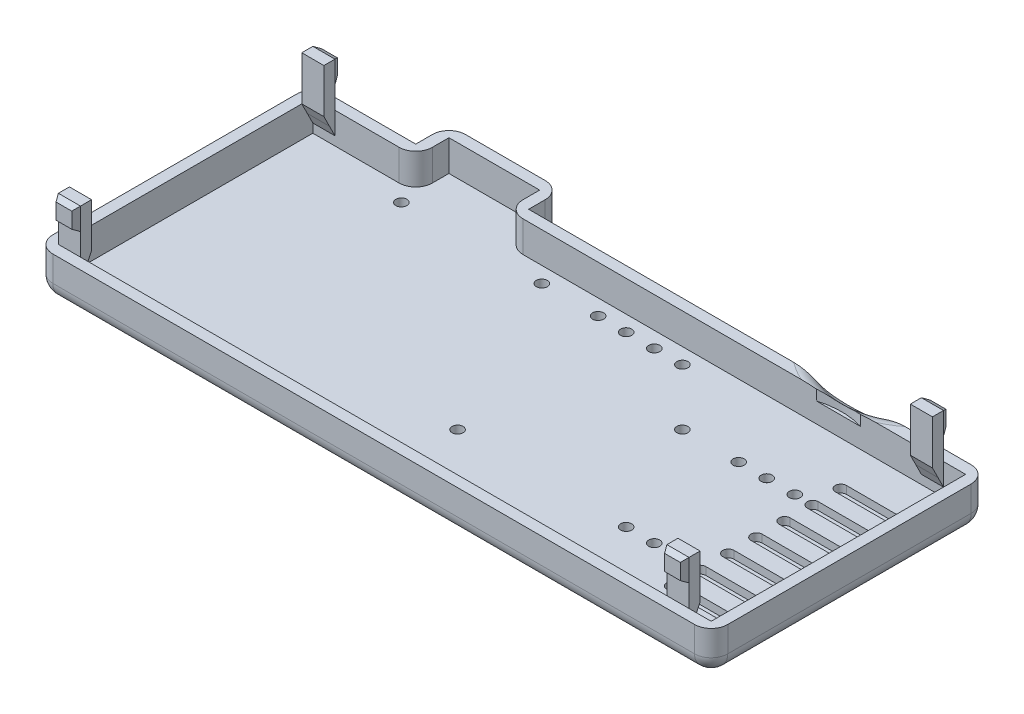
SolidWorks part; units mm, degrees
material "ABS"
ref_plane "Front Plane" through (0, 0, 0) normal (0, 0, 1) x (1, 0, 0)
ref_plane "Top Plane" through (0, 0, 0) normal (0, 1, 0) x (1, 0, 0)
ref_plane "Right Plane" through (0, 0, 0) normal (1, 0, 0) x (0, 0, -1)
sketch "Sketch1" plane through (0, 0, 0) normal (0, 1, 0) x (1, 0, 0)
  line L0 (0, 0) -> (2.54, 0) construction
  line L1 (-5.75, 3.5) -> (64.25, 3.5)
  line L2 (-5.75, 3.5) -> (-5.75, -26.5)
  line L3 (-5.75, -26.5) -> (64.25, -26.5)
  line L4 (64.25, 3.5) -> (64.25, -26.5)
  line L5 (0, 0) -> (0, -2.54) construction
  circle A0 centre (0, 0) radius 0.5 construction
  circle A1 centre (2.54, 0) radius 0.5 construction
  circle A2 centre (5.08, 0) radius 0.5 construction
  circle A3 centre (7.62, 0) radius 0.5 construction
  circle A4 centre (10.16, 0) radius 0.5 construction
  circle A5 centre (12.7, 0) radius 0.5 construction
  circle A6 centre (15.24, 0) radius 0.5 construction
  circle A7 centre (17.78, 0) radius 0.5 construction
  circle A8 centre (20.32, 0) radius 0.5 construction
  circle A9 centre (22.86, 0) radius 0.5 construction
  circle A10 centre (25.4, 0) radius 0.5 construction
  circle A11 centre (27.94, 0) radius 0.5 construction
  circle A12 centre (30.48, 0) radius 0.5 construction
  circle A13 centre (33.02, 0) radius 0.5 construction
  circle A14 centre (35.56, 0) radius 0.5 construction
  circle A15 centre (38.1, 0) radius 0.5 construction
  circle A16 centre (40.64, 0) radius 0.5 construction
  circle A17 centre (43.18, 0) radius 0.5 construction
  circle A18 centre (45.72, 0) radius 0.5 construction
  circle A19 centre (48.26, 0) radius 0.5 construction
  circle A20 centre (50.8, 0) radius 0.5 construction
  circle A21 centre (53.34, 0) radius 0.5 construction
  circle A22 centre (55.88, 0) radius 0.5 construction
  circle A23 centre (58.42, 0) radius 0.5 construction
  circle A24 centre (2.54, -2.54) radius 0.5 construction
  circle A25 centre (5.08, -2.54) radius 0.5 construction
  circle A26 centre (7.62, -2.54) radius 0.5 construction
  circle A27 centre (10.16, -2.54) radius 0.5 construction
  circle A28 centre (12.7, -2.54) radius 0.5
  circle A29 centre (15.24, -2.54) radius 0.5 construction
  circle A30 centre (17.78, -2.54) radius 0.5
  circle A31 centre (20.32, -2.54) radius 0.5
  circle A32 centre (22.86, -2.54) radius 0.5
  circle A33 centre (25.4, -2.54) radius 0.5
  circle A34 centre (27.94, -2.54) radius 0.5 construction
  circle A35 centre (30.48, -2.54) radius 0.5 construction
  circle A36 centre (33.02, -2.54) radius 0.5 construction
  circle A37 centre (35.56, -2.54) radius 0.5 construction
  circle A38 centre (38.1, -2.54) radius 0.5 construction
  circle A39 centre (40.64, -2.54) radius 0.5 construction
  circle A40 centre (43.18, -2.54) radius 0.5 construction
  circle A41 centre (45.72, -2.54) radius 0.5 construction
  circle A42 centre (48.26, -2.54) radius 0.5 construction
  circle A43 centre (50.8, -2.54) radius 0.5 construction
  circle A44 centre (53.34, -2.54) radius 0.5 construction
  circle A45 centre (55.88, -2.54) radius 0.5 construction
  circle A46 centre (58.42, -2.54) radius 0.5 construction
  circle A47 centre (2.54, -5.08) radius 0.5 construction
  circle A48 centre (5.08, -5.08) radius 0.5 construction
  circle A49 centre (7.62, -5.08) radius 0.5 construction
  circle A50 centre (10.16, -5.08) radius 0.5 construction
  circle A51 centre (12.7, -5.08) radius 0.5 construction
  circle A52 centre (15.24, -5.08) radius 0.5 construction
  circle A53 centre (17.78, -5.08) radius 0.5 construction
  circle A54 centre (20.32, -5.08) radius 0.5 construction
  circle A55 centre (22.86, -5.08) radius 0.5 construction
  circle A56 centre (25.4, -5.08) radius 0.5 construction
  circle A57 centre (27.94, -5.08) radius 0.5 construction
  circle A58 centre (30.48, -5.08) radius 0.5 construction
  circle A59 centre (33.02, -5.08) radius 0.5 construction
  circle A60 centre (35.56, -5.08) radius 0.5 construction
  circle A61 centre (38.1, -5.08) radius 0.5 construction
  circle A62 centre (40.64, -5.08) radius 0.5 construction
  circle A63 centre (43.18, -5.08) radius 0.5 construction
  circle A64 centre (45.72, -5.08) radius 0.5
  circle A65 centre (48.26, -5.08) radius 0.5
  circle A66 centre (50.8, -5.08) radius 0.5 construction
  circle A67 centre (53.34, -5.08) radius 0.5 construction
  circle A68 centre (55.88, -5.08) radius 0.5 construction
  circle A69 centre (58.42, -5.08) radius 0.5 construction
  circle A70 centre (2.54, -7.62) radius 0.5 construction
  circle A71 centre (5.08, -7.62) radius 0.5 construction
  circle A72 centre (7.62, -7.62) radius 0.5 construction
  circle A73 centre (10.16, -7.62) radius 0.5 construction
  circle A74 centre (12.7, -7.62) radius 0.5 construction
  circle A75 centre (15.24, -7.62) radius 0.5 construction
  circle A76 centre (17.78, -7.62) radius 0.5 construction
  circle A77 centre (20.32, -7.62) radius 0.5 construction
  circle A78 centre (22.86, -7.62) radius 0.5 construction
  circle A79 centre (25.4, -7.62) radius 0.5 construction
  circle A80 centre (27.94, -7.62) radius 0.5 construction
  circle A81 centre (30.48, -7.62) radius 0.5
  circle A82 centre (33.02, -7.62) radius 0.5 construction
  circle A83 centre (35.56, -7.62) radius 0.5
  circle A84 centre (38.1, -7.62) radius 0.5
  circle A85 centre (40.64, -7.62) radius 0.5
  circle A86 centre (43.18, -7.62) radius 0.5 construction
  circle A87 centre (45.72, -7.62) radius 0.5
  circle A88 centre (48.26, -7.62) radius 0.5
  circle A89 centre (50.8, -7.62) radius 0.5 construction
  circle A90 centre (53.34, -7.62) radius 0.5 construction
  circle A91 centre (55.88, -7.62) radius 0.5 construction
  circle A92 centre (58.42, -7.62) radius 0.5 construction
  circle A93 centre (2.54, -10.16) radius 0.5 construction
  circle A94 centre (5.08, -10.16) radius 0.5 construction
  circle A95 centre (7.62, -10.16) radius 0.5 construction
  circle A96 centre (10.16, -10.16) radius 0.5 construction
  circle A97 centre (12.7, -10.16) radius 0.5 construction
  circle A98 centre (15.24, -10.16) radius 0.5 construction
  circle A99 centre (17.78, -10.16) radius 0.5 construction
  circle A100 centre (20.32, -10.16) radius 0.5 construction
  circle A101 centre (22.86, -10.16) radius 0.5 construction
  circle A102 centre (25.4, -10.16) radius 0.5 construction
  circle A103 centre (27.94, -10.16) radius 0.5 construction
  circle A104 centre (30.48, -10.16) radius 0.5 construction
  circle A105 centre (33.02, -10.16) radius 0.5 construction
  circle A106 centre (35.56, -10.16) radius 0.5 construction
  circle A107 centre (38.1, -10.16) radius 0.5 construction
  circle A108 centre (40.64, -10.16) radius 0.5 construction
  circle A109 centre (43.18, -10.16) radius 0.5 construction
  circle A110 centre (45.72, -10.16) radius 0.5
  circle A111 centre (48.26, -10.16) radius 0.5
  circle A112 centre (50.8, -10.16) radius 0.5 construction
  circle A113 centre (53.34, -10.16) radius 0.5 construction
  circle A114 centre (55.88, -10.16) radius 0.5 construction
  circle A115 centre (58.42, -10.16) radius 0.5 construction
  circle A116 centre (2.54, -12.7) radius 0.5 construction
  circle A117 centre (5.08, -12.7) radius 0.5 construction
  circle A118 centre (7.62, -12.7) radius 0.5 construction
  circle A119 centre (10.16, -12.7) radius 0.5 construction
  circle A120 centre (12.7, -12.7) radius 0.5 construction
  circle A121 centre (15.24, -12.7) radius 0.5 construction
  circle A122 centre (17.78, -12.7) radius 0.5 construction
  circle A123 centre (20.32, -12.7) radius 0.5 construction
  circle A124 centre (22.86, -12.7) radius 0.5 construction
  circle A125 centre (25.4, -12.7) radius 0.5 construction
  circle A126 centre (27.94, -12.7) radius 0.5 construction
  circle A127 centre (30.48, -12.7) radius 0.5 construction
  circle A128 centre (33.02, -12.7) radius 0.5 construction
  circle A129 centre (35.56, -12.7) radius 0.5 construction
  circle A130 centre (38.1, -12.7) radius 0.5 construction
  circle A131 centre (40.64, -12.7) radius 0.5 construction
  circle A132 centre (43.18, -12.7) radius 0.5 construction
  circle A133 centre (45.72, -12.7) radius 0.5
  circle A134 centre (48.26, -12.7) radius 0.5
  circle A135 centre (50.8, -12.7) radius 0.5 construction
  circle A136 centre (53.34, -12.7) radius 0.5 construction
  circle A137 centre (55.88, -12.7) radius 0.5 construction
  circle A138 centre (58.42, -12.7) radius 0.5 construction
  circle A139 centre (2.54, -15.24) radius 0.5 construction
  circle A140 centre (5.08, -15.24) radius 0.5 construction
  circle A141 centre (7.62, -15.24) radius 0.5 construction
  circle A142 centre (10.16, -15.24) radius 0.5 construction
  circle A143 centre (12.7, -15.24) radius 0.5 construction
  circle A144 centre (15.24, -15.24) radius 0.5 construction
  circle A145 centre (17.78, -15.24) radius 0.5 construction
  circle A146 centre (20.32, -15.24) radius 0.5 construction
  circle A147 centre (22.86, -15.24) radius 0.5 construction
  circle A148 centre (25.4, -15.24) radius 0.5 construction
  circle A149 centre (27.94, -15.24) radius 0.5 construction
  circle A150 centre (30.48, -15.24) radius 0.5 construction
  circle A151 centre (33.02, -15.24) radius 0.5 construction
  circle A152 centre (35.56, -15.24) radius 0.5 construction
  circle A153 centre (38.1, -15.24) radius 0.5 construction
  circle A154 centre (40.64, -15.24) radius 0.5 construction
  circle A155 centre (43.18, -15.24) radius 0.5 construction
  circle A156 centre (45.72, -15.24) radius 0.5
  circle A157 centre (48.26, -15.24) radius 0.5
  circle A158 centre (50.8, -15.24) radius 0.5 construction
  circle A159 centre (53.34, -15.24) radius 0.5 construction
  circle A160 centre (55.88, -15.24) radius 0.5 construction
  circle A161 centre (58.42, -15.24) radius 0.5 construction
  circle A162 centre (2.54, -17.78) radius 0.5 construction
  circle A163 centre (5.08, -17.78) radius 0.5 construction
  circle A164 centre (7.62, -17.78) radius 0.5 construction
  circle A165 centre (10.16, -17.78) radius 0.5 construction
  circle A166 centre (12.7, -17.78) radius 0.5 construction
  circle A167 centre (15.24, -17.78) radius 0.5 construction
  circle A168 centre (17.78, -17.78) radius 0.5 construction
  circle A169 centre (20.32, -17.78) radius 0.5
  circle A170 centre (22.86, -17.78) radius 0.5 construction
  circle A171 centre (25.4, -17.78) radius 0.5 construction
  circle A172 centre (27.94, -17.78) radius 0.5 construction
  circle A173 centre (30.48, -17.78) radius 0.5 construction
  circle A174 centre (33.02, -17.78) radius 0.5 construction
  circle A175 centre (35.56, -17.78) radius 0.5
  circle A176 centre (38.1, -17.78) radius 0.5
  circle A177 centre (40.64, -17.78) radius 0.5
  circle A178 centre (43.18, -17.78) radius 0.5 construction
  circle A179 centre (45.72, -17.78) radius 0.5
  circle A180 centre (48.26, -17.78) radius 0.5
  circle A181 centre (50.8, -17.78) radius 0.5 construction
  circle A182 centre (53.34, -17.78) radius 0.5 construction
  circle A183 centre (55.88, -17.78) radius 0.5 construction
  circle A184 centre (58.42, -17.78) radius 0.5 construction
  circle A185 centre (2.54, -20.32) radius 0.5 construction
  circle A186 centre (5.08, -20.32) radius 0.5 construction
  circle A187 centre (7.62, -20.32) radius 0.5 construction
  circle A188 centre (10.16, -20.32) radius 0.5 construction
  circle A189 centre (12.7, -20.32) radius 0.5 construction
  circle A190 centre (15.24, -20.32) radius 0.5 construction
  circle A191 centre (17.78, -20.32) radius 0.5 construction
  circle A192 centre (20.32, -20.32) radius 0.5 construction
  circle A193 centre (62.25, 1.5) radius 1
  circle A194 centre (62.25, -24.5) radius 1
  circle A195 centre (-3.75, -24.5) radius 1
  circle A196 centre (-3.75, 1.5) radius 1
  circle A197 centre (22.86, -20.32) radius 0.5 construction
  circle A198 centre (25.4, -20.32) radius 0.5 construction
  circle A199 centre (27.94, -20.32) radius 0.5 construction
  circle A200 centre (30.48, -20.32) radius 0.5 construction
  circle A201 centre (33.02, -20.32) radius 0.5 construction
  circle A202 centre (35.56, -20.32) radius 0.5 construction
  circle A203 centre (38.1, -20.32) radius 0.5 construction
  circle A204 centre (40.64, -20.32) radius 0.5 construction
  circle A205 centre (43.18, -20.32) radius 0.5 construction
  circle A206 centre (45.72, -20.32) radius 0.5
  circle A207 centre (48.26, -20.32) radius 0.5
  circle A208 centre (50.8, -20.32) radius 0.5 construction
  circle A209 centre (53.34, -20.32) radius 0.5 construction
  circle A210 centre (55.88, -20.32) radius 0.5 construction
  circle A211 centre (58.42, -20.32) radius 0.5 construction
  circle A212 centre (2.54, -22.86) radius 0.5
  circle A213 centre (5.08, -22.86) radius 0.5 construction
  circle A214 centre (7.62, -22.86) radius 0.5
  circle A215 centre (10.16, -22.86) radius 0.5 construction
  circle A216 centre (12.7, -22.86) radius 0.5 construction
  circle A217 centre (15.24, -22.86) radius 0.5 construction
  circle A218 centre (17.78, -22.86) radius 0.5 construction
  circle A219 centre (20.32, -22.86) radius 0.5 construction
  circle A220 centre (22.86, -22.86) radius 0.5
  circle A221 centre (25.4, -22.86) radius 0.5
  circle A222 centre (27.94, -22.86) radius 0.5
  circle A223 centre (30.48, -22.86) radius 0.5
  circle A224 centre (33.02, -22.86) radius 0.5 construction
  circle A225 centre (35.56, -22.86) radius 0.5 construction
  circle A226 centre (38.1, -22.86) radius 0.5 construction
  circle A227 centre (40.64, -22.86) radius 0.5 construction
  circle A228 centre (43.18, -22.86) radius 0.5 construction
  circle A229 centre (45.72, -22.86) radius 0.5 construction
  circle A230 centre (48.26, -22.86) radius 0.5 construction
  circle A231 centre (50.8, -22.86) radius 0.5 construction
  circle A232 centre (53.34, -22.86) radius 0.5 construction
  circle A233 centre (55.88, -22.86) radius 0.5 construction
  circle A234 centre (58.42, -22.86) radius 0.5 construction
  circle A235 centre (0, -2.54) radius 0.5
  circle A236 centre (0, -5.08) radius 0.5 construction
  circle A237 centre (0, -7.62) radius 0.5 construction
  circle A238 centre (0, -10.16) radius 0.5 construction
  circle A239 centre (0, -12.7) radius 0.5 construction
  circle A240 centre (0, -15.24) radius 0.5 construction
  circle A241 centre (0, -17.78) radius 0.5 construction
  circle A242 centre (0, -20.32) radius 0.5 construction
  circle A243 centre (0, -22.86) radius 0.5 construction
  dimension "D1" = 70
  dimension "D2" = 1
  dimension "D4" = 30
  dimension "D5" = 2
  dimension "D7" = 1
  dimension "D8" = 1
  dimension "D9" = 1
  dimension "D10" = 1
  dimension "D11" = 3.5
  dimension "D12" = 5.75
  dimension "D14" = 2.54
  dimension "D15" = 2.54
  dimension "D3" = 24
  dimension "D6" = 10
other "AlignGroup1"
other "AlignGroup2"
extrude "Boss-Extrude1" add sketch "Sketch1" along normal blind 1.5
sketch "Sketch2" plane through (0, 1.5, 0) normal (0, 1, 0) x (1, 0, 0)
  line L0 (-3.75, -25.5) -> (62.25, -25.5) construction
  line L1 (-5.75, -26.5) -> (64.25, -26.5) construction
  line L2 (-2.75, -24.5) -> (-2.75, 1.5) construction
  line L3 (-1.75, 1.5) -> (-1.75, -24.5) construction
  line L4 (-5.75, 3.5) -> (-5.75, -26.5) construction
  circle A0 centre (-3.75, -24.5) radius 1 construction
  circle A1 centre (62.25, -24.5) radius 1 construction
  circle A2 centre (-3.75, 1.5) radius 1 construction
  text T0 "A B C D E F G H I J K L M N O P Q R S T U V W X\r\n" font "Consolas" height 1
  text T1 "01 02 03 04 05 06 07 08 09 10" font "Century Gothic" height 1
  dimension "D2" = 3
  dimension "D1" = 1
  dimension "D3" = 1
extrude "Cut-Extrude1" cut sketch "Sketch2" against normal blind 0.5
sketch "LCD PINS" [suppressed] plane through (0, 0, 0) normal (0, -1, 0) x (1, 0, 0)
  text T0 "          RST" font "Consolas" height 0.5
  text T1 "          CE" font "Consolas" height 0.5
  text T2 "          DC" font "Consolas" height 0.5
  text T3 "          DIN" font "Consolas" height 0.5
  text T4 "          CLK" font "Consolas" height 0.5
  text T5 "          VCC" font "Consolas" height 0.5
  text T6 "         LIGHT" font "Consolas" height 0.5
  text T7 "          GND" font "Consolas" height 0.5
sketch "Sketch3" plane through (0, 1.5, 0) normal (0, 1, 0) x (1, 0, 0)
  line L0 (64.25, -26.5) -> (64.25, 3.5) construction
  line L1 (-0.915, -1.6238) -> (49.085, -1.6238)
  line L2 (-0.915, -1.6238) -> (-0.915, -23.6238)
  line L3 (-0.915, -23.6238) -> (49.085, -23.6238)
  line L4 (49.085, -1.6238) -> (49.085, -23.6238)
  line L5 (64.25, 3.5) -> (-5.75, 3.5) construction
  line L6 (-5.75, -26.5) -> (64.25, -26.5) construction
  line L7 (-5.75, 3.5) -> (-5.75, -26.5) construction
  line L8 (64.25, -26.5) -> (64.25, 3.5)
  line L9 (64.25, 3.5) -> (-5.75, 3.5)
  line L10 (-5.75, -26.5) -> (64.25, -26.5)
  line L11 (-5.75, 3.5) -> (-5.75, -26.5)
  dimension "D1" = 50
  dimension "D2" = 22
extrude "Cut-Extrude2" cut sketch "Sketch3" against normal through all both and the other way through all
sketch "Sketch4" plane through (0, 0, 0) normal (0, -1, 0) x (1, 0, 0)
  line L0 (49.085, 23.6238) -> (49.085, 1.6238) construction
  line L1 (-9.415, 1.1238) -> (49.585, 1.1238)
  line L2 (-9.415, 1.1238) -> (-9.415, 24.1238)
  line L3 (-9.415, 24.1238) -> (49.585, 24.1238)
  line L4 (49.585, 1.1238) -> (49.585, 24.1238)
  line L5 (-0.915, 1.6238) -> (-0.915, 23.6238) construction
  line L6 (-10.415, 0.1238) -> (-10.415, 25.1238)
  line L7 (-10.415, 25.1238) -> (50.585, 25.1238)
  line L8 (50.585, 0.1238) -> (50.585, 25.1238)
  line L9 (-10.415, 0.1238) -> (50.585, 0.1238)
  point P6 (-9.415, 12.6238)
  point P9 (-0.915, 12.6238)
  dimension "D1" = 59
  dimension "D2" = 23
  dimension "D3" = 0.5
  dimension "D4" = 1
extrude "Boss-Extrude2" add sketch "Sketch4" against normal blind 17 separate body
sketch "Sketch5" plane through (0, 0, 0) normal (0, -1, 0) x (1, 0, 0)
  line L0 (-10.415, 0.1238) -> (50.585, 0.1238) construction
  line L1 (50.585, 0.1238) -> (50.585, 25.1238) construction
  line L2 (50.585, 25.1238) -> (-10.415, 25.1238) construction
  line L3 (-10.415, 25.1238) -> (-10.415, 0.1238) construction
  line L4 (-10.415, 0.1238) -> (50.585, 0.1238)
  line L5 (50.585, 0.1238) -> (50.585, 25.1238)
  line L6 (50.585, 25.1238) -> (-10.415, 25.1238)
  line L7 (-10.415, 25.1238) -> (-10.415, 0.1238)
extrude "Boss-Extrude3" add sketch "Sketch5" along normal blind 1
sketch "Sketch6" plane through (0, 0, 0) normal (0, 1, 0) x (1, 0, 0)
  line L0 (48.26, -5.08) -> (42.26, -5.08) construction
  line L1 (48.26, -5.58) -> (42.26, -5.58)
  line L2 (48.26, -4.58) -> (42.26, -4.58)
  line L3 (50.585, -0.1238) -> (50.585, -25.1238) construction
  line L4 (48.26, -7.62) -> (42.26, -7.62) construction
  line L5 (48.26, -8.12) -> (42.26, -8.12)
  line L6 (48.26, -7.12) -> (42.26, -7.12)
  line L7 (48.26, -10.16) -> (42.26, -10.16) construction
  line L8 (48.26, -10.66) -> (42.26, -10.66)
  line L9 (48.26, -9.66) -> (42.26, -9.66)
  line L10 (48.26, -12.7) -> (42.26, -12.7) construction
  line L11 (48.26, -13.2) -> (42.26, -13.2)
  line L12 (48.26, -12.2) -> (42.26, -12.2)
  line L13 (48.26, -15.24) -> (42.26, -15.24) construction
  line L14 (48.26, -15.74) -> (42.26, -15.74)
  line L15 (48.26, -14.74) -> (42.26, -14.74)
  line L16 (48.26, -17.78) -> (42.26, -17.78) construction
  line L17 (48.26, -18.28) -> (42.26, -18.28)
  line L18 (48.26, -17.28) -> (42.26, -17.28)
  line L19 (48.26, -20.32) -> (42.26, -20.32) construction
  line L20 (48.26, -20.82) -> (42.26, -20.82)
  line L21 (48.26, -19.82) -> (42.26, -19.82)
  line L22 (48.26, -5.08) -> (48.26, -7.62) construction
  circle A0 centre (7.62, -22.86) radius 0.5 construction
  circle A1 centre (2.54, -22.86) radius 0.5 construction
  circle A2 centre (20.32, -17.78) radius 0.5 construction
  circle A3 centre (22.86, -22.86) radius 0.5 construction
  circle A4 centre (25.4, -22.86) radius 0.5 construction
  circle A5 centre (27.94, -22.86) radius 0.5 construction
  circle A6 centre (30.48, -22.86) radius 0.5 construction
  circle A7 centre (35.56, -17.78) radius 0.5 construction
  circle A8 centre (38.1, -17.78) radius 0.5 construction
  circle A9 centre (40.64, -17.78) radius 0.5 construction
  circle A20 centre (30.48, -7.62) radius 0.5 construction
  circle A21 centre (35.56, -7.62) radius 0.5 construction
  circle A22 centre (38.1, -7.62) radius 0.5 construction
  circle A23 centre (40.64, -7.62) radius 0.5 construction
  circle A27 centre (45.72, -5.08) radius 0.5 construction
  circle A28 centre (25.4, -2.54) radius 0.5 construction
  circle A29 centre (22.86, -2.54) radius 0.5 construction
  circle A30 centre (20.32, -2.54) radius 0.5 construction
  circle A31 centre (17.78, -2.54) radius 0.5 construction
  circle A32 centre (12.7, -2.54) radius 0.5 construction
  circle A33 centre (0, -2.54) radius 0.5 construction
  circle A34 centre (7.62, -22.86) radius 0.5
  circle A35 centre (2.54, -22.86) radius 0.5
  circle A36 centre (20.32, -17.78) radius 0.5
  circle A37 centre (22.86, -22.86) radius 0.5
  circle A38 centre (25.4, -22.86) radius 0.5
  circle A39 centre (27.94, -22.86) radius 0.5
  circle A40 centre (30.48, -22.86) radius 0.5
  circle A41 centre (35.56, -17.78) radius 0.5
  circle A42 centre (38.1, -17.78) radius 0.5
  circle A43 centre (40.64, -17.78) radius 0.5
  circle A54 centre (30.48, -7.62) radius 0.5
  circle A55 centre (35.56, -7.62) radius 0.5
  circle A56 centre (38.1, -7.62) radius 0.5
  circle A57 centre (40.64, -7.62) radius 0.5
  arc A60 (48.26, -8.12) -> (48.26, -7.12) centre (48.26, -7.62) ccw
  arc A61 (42.26, -7.12) -> (42.26, -8.12) centre (42.26, -7.62) ccw
  circle A62 centre (25.4, -2.54) radius 0.5
  circle A63 centre (22.86, -2.54) radius 0.5
  circle A64 centre (20.32, -2.54) radius 0.5
  circle A65 centre (17.78, -2.54) radius 0.5
  circle A66 centre (12.7, -2.54) radius 0.5
  circle A67 centre (0, -2.54) radius 0.5
  arc A68 (48.26, -5.58) -> (48.26, -4.58) centre (48.26, -5.08) ccw
  arc A69 (42.26, -4.58) -> (42.26, -5.58) centre (42.26, -5.08) ccw
  arc A70 (48.26, -10.66) -> (48.26, -9.66) centre (48.26, -10.16) ccw
  arc A71 (42.26, -9.66) -> (42.26, -10.66) centre (42.26, -10.16) ccw
  arc A72 (48.26, -13.2) -> (48.26, -12.2) centre (48.26, -12.7) ccw
  arc A73 (42.26, -12.2) -> (42.26, -13.2) centre (42.26, -12.7) ccw
  arc A74 (48.26, -15.74) -> (48.26, -14.74) centre (48.26, -15.24) ccw
  arc A75 (42.26, -14.74) -> (42.26, -15.74) centre (42.26, -15.24) ccw
  arc A76 (48.26, -18.28) -> (48.26, -17.28) centre (48.26, -17.78) ccw
  arc A77 (42.26, -17.28) -> (42.26, -18.28) centre (42.26, -17.78) ccw
  arc A78 (48.26, -20.82) -> (48.26, -19.82) centre (48.26, -20.32) ccw
  arc A79 (42.26, -19.82) -> (42.26, -20.82) centre (42.26, -20.32) ccw
  point P102 (45.26, -5.08)
  point P110 (45.26, -7.62)
  point P117 (45.26, -10.16)
  point P124 (45.26, -12.7)
  point P131 (45.26, -15.24)
  point P138 (45.26, -17.78)
  point P145 (45.26, -20.32)
  dimension "D2" = 0.5
  dimension "D3" = 2.325
  dimension "D1" = 6
  dimension "D5" = 2.54
  dimension "D4" = 7
extrude "Cut-Extrude3" cut sketch "Sketch6" against normal blind 0.7
sketch "Sketch8" plane through (0, 1.5, 0) normal (0, 1, 0) x (1, 0, 0)
  line L4 (49.085, -1.6238) -> (-0.915, -1.6238)
  line L5 (-0.915, -1.6238) -> (-0.915, -23.6238)
  line L6 (-0.915, -23.6238) -> (49.085, -23.6238)
  line L7 (49.085, -23.6238) -> (49.085, -1.6238)
  line L8 (49.085, -1.6238) -> (-0.915, -1.6238)
  line L9 (-0.915, -1.6238) -> (-0.915, -23.6238)
  line L10 (-0.915, -23.6238) -> (49.085, -23.6238)
  line L11 (49.085, -23.6238) -> (49.085, -1.6238)
  dimension "D1" = 0
extrude "Cut-Extrude4" cut sketch "Sketch8" against normal up to surface (1.5 mm away) up to face at (24.085, 0, 12.6238)
sketch "Sketch9" plane through (0, 17, 0) normal (0, 1, 0) x (1, 0, 0)
  line L0 (7.585, -0.1238) -> (7.585, 1.8762)
  line L1 (-10.415, -0.1238) -> (50.585, -0.1238) construction
  line L2 (7.585, 1.8762) -> (-9.415, 1.8762)
  line L3 (-9.415, 1.8762) -> (-9.415, -0.1238)
  line L4 (-9.415, -0.1238) -> (-10.415, -0.1238)
  line L5 (-10.415, -0.1238) -> (-10.415, 2.8762)
  line L6 (-10.415, 2.8762) -> (8.585, 2.8762)
  line L7 (8.585, 2.8762) -> (8.585, -0.1238)
  line L8 (8.585, -0.1238) -> (7.585, -0.1238)
  line L10 (-9.415, -24.1238) -> (-9.415, -1.1238) construction
  dimension "D1" = 1
  dimension "D2" = 1
  dimension "D3" = 1
  dimension "D4" = 2
  dimension "D5" = 17
extrude "Boss-Extrude4" add sketch "Sketch9" against normal up to surface (18 mm away) up to face at (20.085, -1, 12.6238)
sketch "Sketch10" plane through (0, -1, 0) normal (0, -1, 0) x (1, 0, 0)
  line L0 (7.585, -1.8762) -> (7.585, 0.1238) construction
  line L1 (-9.415, -1.8762) -> (7.585, -1.8762) construction
  line L2 (-9.415, 0.1238) -> (-9.415, -1.8762) construction
  line L3 (-9.415, 0.1238) -> (7.585, 0.1238) construction
  line L4 (7.585, -1.8762) -> (7.585, 0.1238)
  line L5 (-9.415, -1.8762) -> (7.585, -1.8762)
  line L6 (-9.415, 0.1238) -> (-9.415, -1.8762)
  line L7 (-9.415, 0.1238) -> (7.585, 0.1238)
extrude "Boss-Extrude5" add sketch "Sketch10" against normal up to surface (1 mm away) up to face at (20.085, 0, 12.6238)
sketch "Sketch11" plane through (0, 17, 0) normal (0, 1, 0) x (1, 0, 0)
  line L0 (-9.415, -0.1238) -> (7.585, -0.1238) construction
  line L1 (-9.415, -0.1238) -> (7.585, -0.1238)
  line L2 (-9.415, -1.1238) -> (49.585, -1.1238) construction
  line L3 (-9.415, -1.1238) -> (7.585, -1.1238)
  line L4 (7.585, -1.1238) -> (7.585, -0.1238)
  line L5 (-9.415, -1.1238) -> (-9.415, -0.1238)
extrude "Cut-Extrude5" cut sketch "Sketch11" against normal up to surface (17 mm away) up to face at (20.085, 0, 12.6238)
sketch "Sketch12" plane through (0, 0, 25.1238) normal (0, 0, 1) x (1, 0, 0)
  line L0 (50.585, -1) -> (-10.415, -1) construction
  line L1 (36.285, 4.5) -> (39.785, 4.5)
  line L2 (36.285, 4.5) -> (36.285, 3)
  line L3 (36.285, 3) -> (39.785, 3)
  line L4 (39.785, 4.5) -> (39.785, 3)
  line L5 (50.585, -1) -> (50.585, 17) construction
  line L6 (39.785, 4.5) -> (39.785, -1) construction
  line L8 (39.785, -1) -> (36.285, -1) construction
  line L9 (36.285, -1) -> (36.285, 4.5) construction
  dimension "D1" = 3.5
  dimension "D2" = 1.5
  dimension "D3" = 4
  dimension "D4" = 10.8
extrude "Cut-Extrude6" cut sketch "Sketch12" against normal up to surface (1 mm away) up to face at (20.085, 8.5, 24.1238)
sketch "Sketch13" plane through (0, 0, 0.1238) normal (0, 0, -1) x (-1, 0, 0)
  line L0 (-8.585, -1) -> (-50.585, -1) construction
  line L1 (-40.985, 6) -> (-35.285, 6)
  line L2 (-40.985, 6) -> (-40.985, 3)
  line L3 (-40.985, 3) -> (-35.285, 3)
  line L4 (-35.285, 6) -> (-35.285, 3)
  line L5 (-50.585, -1) -> (-50.585, 17) construction
  dimension "D1" = 3
  dimension "D2" = 7
  dimension "D3" = 5.7
  dimension "D4" = 9.6
extrude "Cut-Extrude7" cut sketch "Sketch13" against normal up to surface (1 mm away) up to face at (28.585, 8.5, 1.1238)
sketch "Sketch14" plane through (0, 3, 0) normal (0, 1, 0) x (1, 0, 0)
  line L4 (35.285, -1.1238) -> (40.985, -1.1238)
  line L5 (40.985, -1.1238) -> (40.985, -0.1238)
  line L6 (40.985, -0.1238) -> (35.285, -0.1238)
  line L7 (35.285, -0.1238) -> (35.285, -1.1238)
  line L8 (35.285, -1.1238) -> (40.985, -1.1238)
  line L9 (40.985, -1.1238) -> (40.985, -0.1238)
  line L10 (40.985, -0.1238) -> (35.285, -0.1238)
  line L11 (35.285, -0.1238) -> (35.285, -1.1238)
  dimension "D1" = 0
extrude "Cut-Extrude8" cut sketch "Sketch14" against normal blind 0.2
sketch "Sketch15" plane through (0, 17, 0) normal (0, 1, 0) x (1, 0, 0)
  line L0 (50.585, -25.1238) -> (-10.415, -25.1238) construction
  line L1 (49.585, -24.1238) -> (-9.415, -24.1238) construction
  line L2 (50.585, -0.1238) -> (50.585, -25.1238) construction
  line L3 (49.585, -1.1238) -> (49.585, -24.1238) construction
  line L4 (7.585, -1.1238) -> (49.585, -1.1238) construction
  line L5 (8.585, -0.1238) -> (50.585, -0.1238) construction
  line L6 (50.585, -25.1238) -> (-9.415, -25.1238)
  line L7 (49.585, -24.1238) -> (-9.415, -24.1238)
  line L8 (50.585, -0.1238) -> (50.585, -25.1238)
  line L9 (49.585, -1.1238) -> (49.585, -24.1238)
  line L10 (10.585, -1.1238) -> (49.585, -1.1238)
  line L11 (10.585, -0.1238) -> (50.585, -0.1238)
  line L12 (-9.415, -25.1238) -> (-9.415, -24.1238)
  line L13 (10.585, -0.1238) -> (10.585, -1.1238)
  dimension "D1" = 40
extrude "Cut-Extrude9" cut sketch "Sketch15" against normal blind 2.8
sketch "Sketch16" plane through (0, 14.2, 0) normal (0, 1, 0) x (1, 0, 0)
  line L0 (10.585, -1.1238) -> (49.585, -1.1238) construction
  line L1 (50.585, -0.1238) -> (10.585, -0.1238) construction
  line L2 (49.585, -24.1238) -> (-9.415, -24.1238) construction
  line L3 (-9.415, -25.1238) -> (50.585, -25.1238) construction
  line L4 (26.085, -0.1238) -> (26.085, -1.1238)
  line L5 (26.085, -25.1238) -> (26.085, -24.1238)
  line L8 (50.585, -25.1238) -> (50.585, -0.1238)
  line L9 (50.585, -0.1238) -> (10.585, -0.1238)
  line L10 (10.585, -0.1238) -> (10.585, -1.1238)
  line L11 (10.585, -1.1238) -> (49.585, -1.1238)
  line L12 (49.585, -1.1238) -> (49.585, -24.1238)
  line L13 (49.585, -24.1238) -> (-9.415, -24.1238)
  line L14 (-9.415, -24.1238) -> (-9.415, -25.1238)
  line L15 (-9.415, -25.1238) -> (50.585, -25.1238)
  line L16 (50.585, -25.1238) -> (50.585, -0.1238)
  line L17 (50.585, -0.1238) -> (26.085, -0.1238)
  line L19 (26.085, -1.1238) -> (49.585, -1.1238)
  line L20 (49.585, -1.1238) -> (49.585, -24.1238)
  line L21 (49.585, -24.1238) -> (26.085, -24.1238)
  line L23 (26.085, -25.1238) -> (50.585, -25.1238)
  dimension "D2" = 24.5
  dimension "D1" = 0
extrude "Boss-Extrude6" add sketch "Sketch16" along normal blind 0.9
sketch "Sketch17" plane through (0, 15.1, 0) normal (0, 1, 0) x (1, 0, 0)
  line L0 (26.085, -1.1238) -> (49.585, -1.1238) construction
  line L1 (26.085, -1.1238) -> (49.585, -1.1238)
  line L2 (49.585, -1.1238) -> (49.585, -24.1238) construction
  line L3 (26.085, -24.1238) -> (26.085, -25.1238) construction
  line L4 (49.585, -24.1238) -> (26.085, -24.1238) construction
  line L6 (49.585, -1.1238) -> (49.585, -24.1238) construction
  line L7 (26.085, -24.1238) -> (26.085, -1.1238)
  line L8 (49.585, -24.1238) -> (26.085, -24.1238)
  line L9 (31.085, -1.1238) -> (31.085, -24.1238) construction
  line L10 (44.585, -1.1238) -> (44.585, -24.1238) construction
  line L11 (49.585, -3.6638) -> (47.045, -3.6638)
  line L12 (47.045, -3.6638) -> (47.045, -21.5838)
  line L13 (47.045, -21.5838) -> (49.585, -21.5838)
  line L14 (31.085, -3.1238) -> (44.585, -3.1238)
  line L15 (31.085, -22.1238) -> (44.585, -22.1238)
  line L16 (31.085, -3.1238) -> (31.085, -22.1238)
  line L17 (44.585, -3.1238) -> (44.585, -22.1238)
  line L18 (49.585, -3.6638) -> (49.585, -1.1238)
  line L19 (49.585, -21.5838) -> (49.585, -24.1238)
  dimension "D1" = 5
  dimension "D2" = 5
  dimension "D3" = 2.54
  dimension "D4" = 2.54
  dimension "D5" = 2.54
  dimension "D6" = 2
  dimension "D7" = 2
extrude "Boss-Extrude7" add sketch "Sketch17" against normal blind 1
sketch "Sketch18" [suppressed] plane through (0, 3, 0) normal (0, 1, 0) x (1, 0, 0)
  line L4 (39.785, -24.1238) -> (36.285, -24.1238)
  line L5 (36.285, -24.1238) -> (36.285, -25.1238)
  line L6 (36.285, -25.1238) -> (39.785, -25.1238)
  line L7 (39.785, -25.1238) -> (39.785, -24.1238)
  line L8 (39.785, -24.1238) -> (36.285, -24.1238)
  line L9 (36.285, -24.1238) -> (36.285, -25.1238)
  line L10 (36.285, -25.1238) -> (39.785, -25.1238)
  line L11 (39.785, -25.1238) -> (39.785, -24.1238)
  dimension "D1" = 0
extrude "Cut-Extrude10" [suppressed] cut sketch "Sketch18" against normal blind 0.2
sketch "Sketch19" [suppressed] plane through (0, 0, 25.1238) normal (0, 0, 1) x (1, 0, 0)
  line L0 (36.285, 2.8) -> (39.785, 2.8) construction
  line L1 (-10.415, 2.8) -> (50.585, 2.8)
  line L2 (-10.415, -1) -> (-10.415, 17) construction
  line L3 (50.585, -1) -> (50.585, 15.1) construction
  line L4 (-10.415, 2.8) -> (-10.415, 17)
  line L5 (-10.415, 17) -> (50.585, 17)
  line L6 (50.585, 17) -> (50.585, 2.8)
extrude "Cut-Extrude11" [suppressed] cut sketch "Sketch19" against normal through all both and the other way through all
sketch "Sketch20" plane through (0, 0, 25.1238) normal (0, 0, 1) x (1, 0, 0)
  line L0 (36.285, 3) -> (39.785, 3) construction
  line L1 (-10.415, 3) -> (50.585, 3)
  line L2 (50.585, -1) -> (50.585, 15.1) construction
  line L3 (-10.415, -1) -> (-10.415, 17) construction
  line L6 (-10.415, 17) -> (-10.415, 3)
  line L7 (50.585, 17) -> (50.585, 3)
  line L10 (50.585, 17) -> (-10.415, 17)
extrude "Cut-Extrude12" cut sketch "Sketch20" against normal through all both and the other way through all
sketch "Sketch21" plane through (0, 3, 0) normal (0, 1, 0) x (1, 0, 0)
  line L16 (49.585, -24.1238) -> (-9.415, -24.1238)
  line L17 (-9.415, -24.1238) -> (-9.415, 1.8762)
  line L18 (-9.415, 1.8762) -> (7.585, 1.8762)
  line L19 (7.585, 1.8762) -> (7.585, -1.1238)
  line L20 (7.585, -1.1238) -> (35.285, -1.1238)
  line L21 (35.285, -1.1238) -> (35.285, -0.1238)
  line L22 (35.285, -0.1238) -> (8.585, -0.1238)
  line L23 (8.585, -0.1238) -> (8.585, 2.8762)
  line L24 (8.585, 2.8762) -> (-10.415, 2.8762)
  line L25 (-10.415, 2.8762) -> (-10.415, -25.1238)
  line L26 (-10.415, -25.1238) -> (50.585, -25.1238)
  line L27 (50.585, -25.1238) -> (50.585, -0.1238)
  line L28 (50.585, -0.1238) -> (40.985, -0.1238)
  line L29 (40.985, -0.1238) -> (40.985, -1.1238)
  line L30 (40.985, -1.1238) -> (49.585, -1.1238)
  line L31 (49.585, -1.1238) -> (49.585, -24.1238)
  line L32 (49.585, -24.1238) -> (-9.415, -24.1238)
  line L33 (-9.415, -24.1238) -> (-9.415, 1.8762)
  line L34 (-9.415, 1.8762) -> (7.585, 1.8762)
  line L35 (7.585, 1.8762) -> (7.585, -1.1238)
  line L36 (7.585, -1.1238) -> (35.285, -1.1238)
  line L37 (35.285, -1.1238) -> (35.285, -0.1238)
  line L38 (35.285, -0.1238) -> (8.585, -0.1238)
  line L39 (8.585, -0.1238) -> (8.585, 2.8762)
  line L40 (8.585, 2.8762) -> (-10.415, 2.8762)
  line L41 (-10.415, 2.8762) -> (-10.415, -25.1238)
  line L42 (-10.415, -25.1238) -> (50.585, -25.1238)
  line L43 (50.585, -25.1238) -> (50.585, -0.1238)
  line L44 (50.585, -0.1238) -> (40.985, -0.1238)
  line L45 (40.985, -0.1238) -> (40.985, -1.1238)
  line L46 (40.985, -1.1238) -> (49.585, -1.1238)
  line L47 (49.585, -1.1238) -> (49.585, -24.1238)
  dimension "D1" = 0
extrude "Cut-Extrude13" cut sketch "Sketch21" against normal blind 0.2
sketch "Sketch22" plane through (0, 2.8, 0) normal (0, 1, 0) x (1, 0, 0)
  line L0 (8.585, 2.8762) -> (-10.415, 2.8762) construction
  line L1 (-1.115, 2.8762) -> (-10.415, 2.8762)
  line L2 (-10.415, 2.8762) -> (-10.415, -25.1238) construction
  line L3 (-10.415, 2.8762) -> (-10.415, -0.1238)
  line L6 (-10.415, -0.1238) -> (-1.115, -0.1238)
  line L7 (-1.115, -0.1238) -> (-1.115, 2.8762)
  dimension "D1" = 9.3
  dimension "D2" = 3
extrude "Cut-Extrude14" cut sketch "Sketch22" against normal through all both and the other way through all
sketch "Sketch23" plane through (7.585, 0, 0) normal (-1, 0, 0) x (0, 0, 1)
  line L4 (1.1238, 2.8) -> (-1.8762, 2.8)
  line L5 (-1.8762, 2.8) -> (-1.8762, 0)
  line L6 (-1.8762, 0) -> (1.1238, 0)
  line L7 (1.1238, 0) -> (1.1238, 2.8)
  line L8 (1.1238, 2.8) -> (-1.8762, 2.8)
  line L9 (-1.8762, 2.8) -> (-1.8762, 0)
  line L10 (-1.8762, 0) -> (1.1238, 0)
  line L11 (1.1238, 0) -> (1.1238, 2.8)
  dimension "D1" = 0
extrude "Cut-Extrude15" cut sketch "Sketch23" against normal blind 0.5
sketch "Sketch24" plane through (8.585, 0, 0) normal (1, 0, 0) x (0, 0, -1)
  line L4 (2.8762, 2.8) -> (-0.1238, 2.8)
  line L5 (-0.1238, 2.8) -> (-0.1238, -1)
  line L6 (-0.1238, -1) -> (2.8762, -1)
  line L7 (2.8762, -1) -> (2.8762, 2.8)
  line L8 (2.8762, 2.8) -> (-0.1238, 2.8)
  line L9 (-0.1238, 2.8) -> (-0.1238, -1)
  line L10 (-0.1238, -1) -> (2.8762, -1)
  line L11 (2.8762, -1) -> (2.8762, 2.8)
  dimension "D1" = 0
extrude "Boss-Extrude8" add sketch "Sketch24" along normal blind 0.5
sketch "Sketch25" plane through (0, 0, 0) normal (0, 1, 0) x (1, 0, 0)
  line L0 (-1.115, 1.8762) -> (-1.115, -0.1238) construction
  line L1 (-1.115, -0.1238) -> (-9.415, -0.1238) construction
  line L2 (-1.115, 1.8762) -> (-1.115, -0.1238)
  line L3 (-1.115, -0.1238) -> (-9.415, -0.1238)
  line L4 (-1.115, 1.8762) -> (8.085, 1.8762) construction
  line L5 (-1.115, 1.8762) -> (-0.115, 1.8762)
  line L7 (-9.415, -0.1238) -> (-9.415, -1.1238)
  line L8 (-9.415, -24.1238) -> (-9.415, -0.1238) construction
  line L9 (-9.415, -1.1238) -> (-0.115, -1.1238)
  line L10 (-0.115, -1.1238) -> (-0.115, 1.8762)
  dimension "D1" = 1
  dimension "D2" = 1
extrude "Boss-Extrude9" add sketch "Sketch25" along normal up to surface (2.8 mm away) up to face at (13.7707, 2.8, 6.5524)
fillet "Fillet1" radius 1.5 14 edges at (50.585, 0.9, 25.1238) (50.585, 0.9, 0.1238) (50.585, -1, 12.6238) (29.835, -1, 0.1238) (9.085, -1, -1.3762) (9.085, 0.9, -2.8762) (-1.115, 0.9, -2.8762) (3.985, -1, -2.8762) (-1.115, -1, -1.3762) (-10.415, 0.9, 0.1238) (-5.765, -1, 0.1238) (-10.415, -1, 12.6238) (20.085, -1, 25.1238) (-10.415, 0.9, 25.1238)
sketch "Sketch26" plane through (0, 2.8, 0) normal (0, 1, 0) x (1, 0, 0)
  line L0 (8.085, -1.1238) -> (49.585, -1.1238) construction
  line L1 (45.5426, -0.6238) -> (32.2525, -0.6238) construction
  line L2 (36.085, -0.1238) -> (40.085, -0.1238)
  line L3 (36.085, -1.1238) -> (40.085, -1.1238)
  arc A0 (36.085, -1.1238) -> (40.085, -1.1238) centre (38.085, -7.6405) cw
  arc A1 (36.085, -0.1238) -> (40.085, -0.1238) centre (38.085, 6.3928) ccw
  point P3 (38.085, -0.8238)
  dimension "D1" = 4
  dimension "D2" = 0.3
  dimension "D3" = 9.5
  dimension "D4" = 0.5
extrude "Cut-Extrude16" cut sketch "Sketch26" against normal blind 1
sketch "Sketch27" plane through (0, 2.8, 0) normal (0, 1, 0) x (1, 0, 0)
  line L1 (-9.415, -1.1238) -> (-7.415, -1.1238)
  line L2 (-9.415, -1.1238) -> (-9.415, -2.1238)
  line L3 (-9.415, -2.1238) -> (-7.415, -2.1238)
  line L4 (-7.415, -1.1238) -> (-7.415, -2.1238)
  line L5 (-9.415, -24.1238) -> (-7.415, -24.1238)
  line L6 (-9.415, -24.1238) -> (-9.415, -23.1238)
  line L7 (-9.415, -23.1238) -> (-7.415, -23.1238)
  line L8 (-7.415, -24.1238) -> (-7.415, -23.1238)
  line L9 (47.585, -23.1238) -> (45.585, -23.1238)
  line L10 (47.585, -23.1238) -> (47.585, -24.1238)
  line L11 (47.585, -24.1238) -> (45.585, -24.1238)
  line L12 (45.585, -23.1238) -> (45.585, -24.1238)
  line L14 (49.585, -1.1238) -> (49.585, -24.1238) construction
  line L16 (45.585, -1.1238) -> (47.585, -1.1238)
  line L17 (45.585, -1.1238) -> (45.585, -2.1238)
  line L18 (45.585, -2.1238) -> (47.585, -2.1238)
  line L19 (47.585, -1.1238) -> (47.585, -2.1238)
  line L20 (49.585, -24.1238) -> (-9.415, -24.1238) construction
  line L21 (40.085, -1.1238) -> (49.585, -1.1238) construction
  dimension "D1" = 2
  dimension "D2" = 1
  dimension "D3" = 1
  dimension "D4" = 2
  dimension "D5" = 1
  dimension "D6" = 2
  dimension "D8" = 2
  dimension "D9" = 2
  dimension "D10" = 1
  dimension "D12" = 2
extrude "Boss-Extrude10" add sketch "Sketch27" against normal offset from surface 1.8 and the other way blind 4 up to face at (45.26, 0, 5.08)
sketch "Sketch28" plane through (0, 0, 24.1238) normal (0, 0, 1) x (1, 0, 0)
  line L0 (-7.415, 6.8) -> (-7.415, 2.8) construction
  line L1 (-9.415, 6.8) -> (-7.415, 6.8)
  line L2 (-9.415, 6.8) -> (-9.415, 4.8)
  line L3 (-9.415, 4.8) -> (-7.415, 4.8)
  line L4 (-7.415, 6.8) -> (-7.415, 4.8)
  line L5 (47.585, 6.8) -> (47.585, 2.8) construction
  line L6 (45.585, 6.8) -> (47.585, 6.8)
  line L7 (45.585, 6.8) -> (45.585, 4.8)
  line L8 (45.585, 4.8) -> (47.585, 4.8)
  line L9 (47.585, 6.8) -> (47.585, 4.8)
extrude "Boss-Extrude11" add sketch "Sketch28" along normal blind 0.5 draft 30
chamfer "Chamfer1" distance 0.5 distance2 1 8 edges at (-8.415, 1.8, 23.1238) (-8.415, 1.8, 24.1238) (-8.415, 1.8, 2.1238) (46.585, 1.8, 23.1238) (46.585, 1.8, 24.1238) (46.585, 1.8, 1.1238) (46.585, 1.8, 2.1238) (-8.415, 1.8, 1.1238)
sketch "Sketch29" plane through (0, 0, 1.1238) normal (0, 0, -1) x (-1, 0, 0)
  line L0 (-45.585, 6.8) -> (-45.585, 2.8) construction
  line L1 (-47.585, 6.8) -> (-45.585, 6.8)
  line L2 (-47.585, 6.8) -> (-47.585, 4.8)
  line L3 (-47.585, 4.8) -> (-45.585, 4.8)
  line L4 (-45.585, 6.8) -> (-45.585, 4.8)
  line L5 (9.415, 6.8) -> (9.415, 2.8) construction
  line L6 (7.415, 6.8) -> (9.415, 6.8)
  line L7 (7.415, 6.8) -> (7.415, 4.8)
  line L8 (7.415, 4.8) -> (9.415, 4.8)
  line L9 (9.415, 6.8) -> (9.415, 4.8)
extrude "Boss-Extrude12" add sketch "Sketch29" along normal blind 0.5
chamfer "Chamfer2" distance 0.5 angle 30 8 edges at (-8.415, 6.8, 0.6238) (-9.415, 5.8, 0.6238) (-8.415, 4.8, 0.6238) (-7.415, 5.8, 0.6238) (46.585, 6.8, 0.6238) (45.585, 5.8, 0.6238) (46.585, 4.8, 0.6238) (47.585, 5.8, 0.6238)
fillet "Fillet2" radius 1.5 2 edges at (8.085, 1.4, 1.1238) (-0.115, 1.4, 1.1238)
fillet "Fillet3" radius 1.5 1 edges at (38.085, 2.8, 0.4238)
fillet "Fillet4" radius 1.5 1 edges at (38.085, 1.8, 0.4238)
